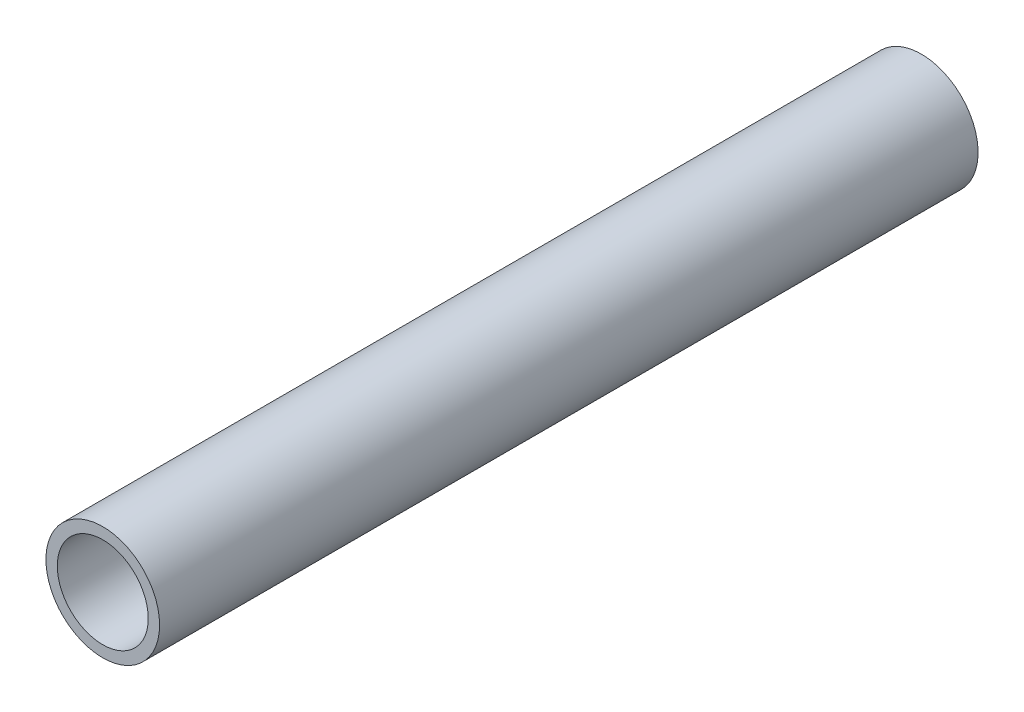
SolidWorks part; units mm, degrees
ref_plane "Plano frontal" through (0, 0, 0) normal (0, 0, 1) x (1, 0, 0)
ref_plane "Plano superior" through (0, 0, 0) normal (0, 1, 0) x (1, 0, 0)
ref_plane "Plano direito" through (0, 0, 0) normal (1, 0, 0) x (0, 0, -1)
sketch "Esboço1" plane through (0, 0, 0) normal (0, 0, 1) x (1, 0, 0)
  circle A0 centre (0, 0) radius 12.5
  circle A1 centre (0, 0) radius 10
  dimension "D1" = 25
  dimension "D2" = 20
extrude "Ressalto-extrusão1" add sketch "Esboço1" along normal blind 180
sketch "Esboço2" plane through (0, 0, 0) normal (1, 0, 0) x (0, 0, -1)
  line L0 (0, -12.5) -> (0, 12.5) construction
  line L1 (0, 0) -> (32.0551, 0) construction
  circle A0 centre (5, 0) radius 12
  circle A1 centre (5, 0) radius 12.5
  dimension "D1" = 24
  dimension "D2" = 25
  dimension "D3" = 5
extrude "Corte-extrusão1" cut sketch "Esboço2" against normal blind 5 and the other way blind 5
